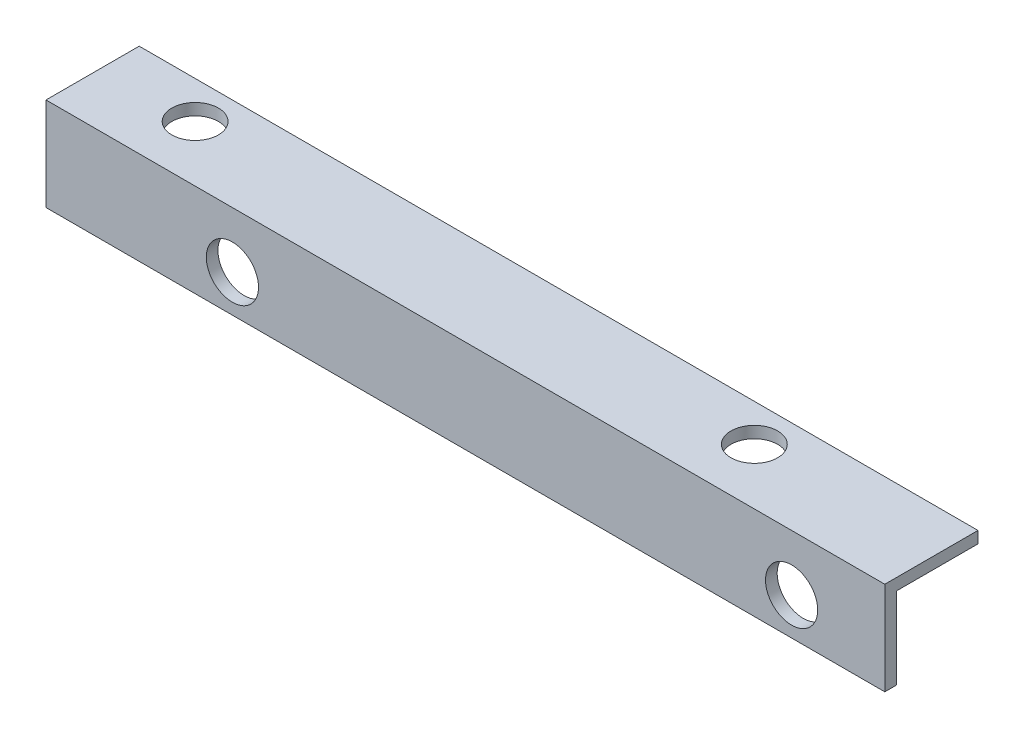
SolidWorks part; units mm, degrees
ref_plane "Front Plane" through (0, 0, 0) normal (0, 0, 1) x (1, 0, 0)
ref_plane "Top Plane" through (0, 0, 0) normal (0, 1, 0) x (1, 0, 0)
ref_plane "Right Plane" through (0, 0, 0) normal (1, 0, 0) x (0, 0, -1)
sketch "Sketch1" plane through (0, 0, 0) normal (1, 0, 0) x (0, 0, -1)
  line L0 (0, 0) -> (0, 12.7)
  line L1 (0, 55) -> (0, -55) construction
  line L2 (0, 12.7) -> (12.7, 12.7)
  line L3 (1.5875, 0) -> (1.5875, 11.1125)
  line L4 (1.5875, 11.1125) -> (12.7, 11.1125)
  line L5 (12.7, 12.7) -> (12.7, 11.1125)
  line L6 (0, 0) -> (1.5875, 0)
  dimension "D1" = 12.7
  dimension "D2" = 12.7
  dimension "D3" = 1.5875
extrude "Boss-Extrude1" add sketch "Sketch1" along normal blind 57.15 and the other way blind 57.15
sketch "Sketch3" plane through (0, 0, 0) normal (0, 0, 1) x (1, 0, 0)
  line L0 (-57.15, 12.7) -> (57.15, 12.7) construction
  line L1 (57.15, 12.7) -> (57.15, 0) construction
  line L2 (-31.75, 5.08) -> (44.45, 5.08) construction
  circle A0 centre (-31.75, 5.08) radius 3.556
  circle A1 centre (44.45, 5.08) radius 3.556
  dimension "D1" = 7.112
  dimension "D2" = 7.62
  dimension "D3" = 76.2
  dimension "D4" = 12.7
extrude "Cut-Extrude1" cut sketch "Sketch3" against normal through all
sketch "Sketch4" plane through (0, 12.7, 0) normal (0, 1, 0) x (1, 0, 0)
  line L0 (-57.15, 12.7) -> (-57.15, 0) construction
  line L1 (-57.15, 12.7) -> (57.15, 12.7) construction
  line L2 (-44.45, 7.62) -> (31.75, 7.62) construction
  circle A0 centre (-44.45, 7.62) radius 3.175
  circle A1 centre (31.75, 7.62) radius 3.175
  dimension "D1" = 6.35
  dimension "D2" = 76.2
  dimension "D3" = 12.7
  dimension "D4" = 5.08
extrude "Cut-Extrude2" cut sketch "Sketch4" against normal through all
